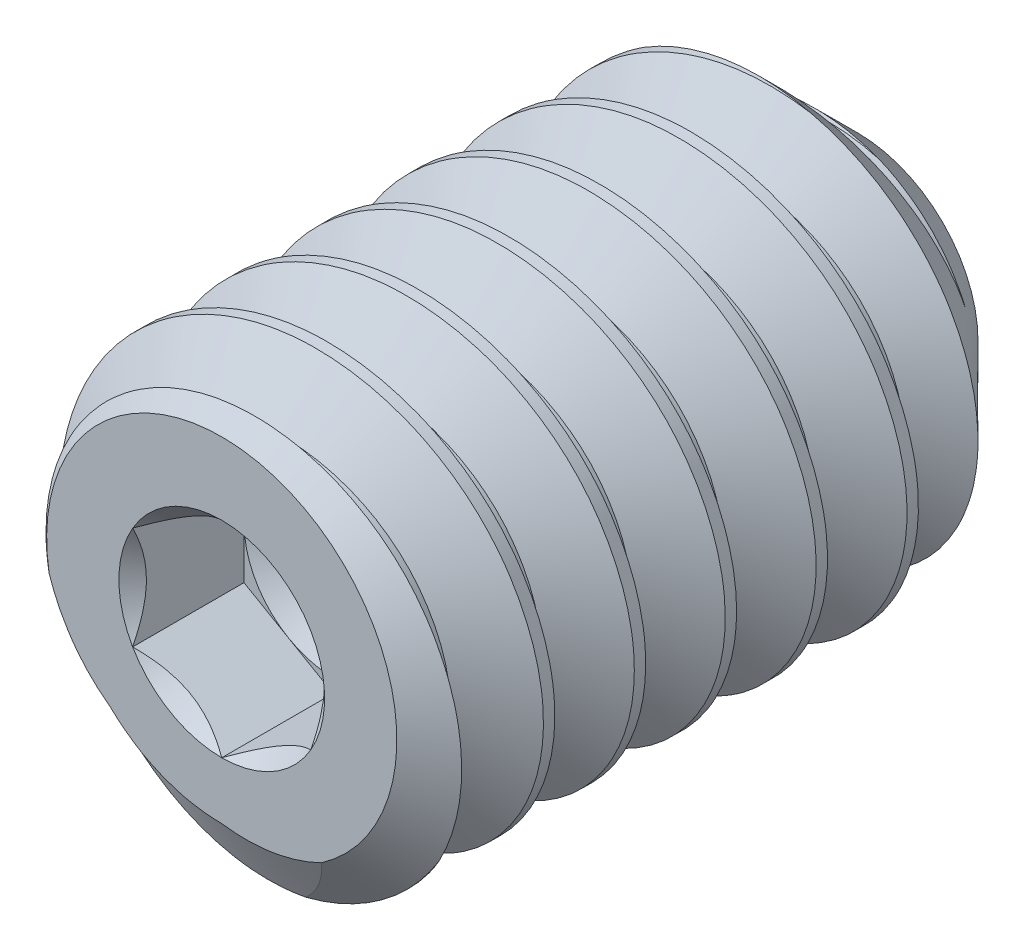
SolidWorks part; units mm, degrees
ref_plane "Front" through (0, 0, 0) normal (0, 0, 1) x (1, 0, 0)
ref_plane "Top" through (0, 0, 0) normal (0, 1, 0) x (1, 0, 0)
ref_plane "Right" through (0, 0, 0) normal (1, 0, 0) x (0, 0, -1)
sketch "Sketch22" plane through (0, 0, 0) normal (1, 0, 0) x (0, 0, -1)
  line L0 (-1.4077, 0) -> (-1.4077, 0.8738)
  line L1 (-1.4077, 0.8738) -> (-1.2547, 1.0922)
  line L2 (-1.2547, 1.0922) -> (1.2736, 1.0922)
  line L3 (1.2736, 1.0922) -> (1.7673, 0.5985)
  line L4 (1.7673, 0.5985) -> (1.4077, 0)
  line L5 (1.4077, 0) -> (-1.4077, 0)
  line L6 (1.4077, 0) -> (1.7673, 0) construction
  line L7 (1.7673, 0) -> (1.7673, 0.5985) construction
  line L8 (1.7673, -0.5985) -> (1.4077, 0) construction
  line L9 (-1.2547, -1.0922) -> (1.2736, -1.0922) construction
  dimension "Dia" = 2.1844
  dimension "Length" = 3.175
  dimension "D3" = 35
  dimension "D5" = 118
  dimension "D6" = 45
  dimension "D7" = 1.7475
revolve "Revolve1" add sketch "Sketch22" angle 360 about L6
ref_plane "Plane1" through (0, 0, -1.7673) normal (0, 0, 1) x (1, 0, 0)
sketch "Sketch27" plane through (0, 0, -1.7673) normal (0, 0, 1) x (1, 0, 0)
  circle A0 centre (0, 0) radius 1.0922 construction
  circle A1 centre (0, 0) radius 1.0922
curve "Helix/Spiral1" pitch 0.4536 height 3.6286 radius 1.0922 centre (0, 0, -1.7673) axis (0, 0, 1) start towards (0, 1, 0)
sketch "Sketch28" plane through (0, 0, 0) normal (1, 0, 0) x (0, 0, -1)
  line L0 (1.7673, 1.0922) -> (2.1642, 1.0922)
  line L1 (2.1642, 1.0922) -> (1.9941, 0.7976)
  line L2 (1.9941, 0.7976) -> (1.9374, 0.7976)
  line L3 (1.9374, 0.7976) -> (1.7673, 1.0922)
  line L4 (1.8523, 0.9449) -> (2.0791, 0.9449) construction
  line L6 (-1.2547, 1.0922) -> (1.2736, 1.0922) construction
  line L7 (1.7673, 1.2014) -> (1.7673, -1.2014) construction
  dimension "D3" = 60
  dimension "D2" = 0.2268
sweep "Cut-Sweep2" cut profiles "Sketch28" path "Helix/Spiral1" align with end faces yes
sketch "Sketch23" plane through (0, 0, 1.4077) normal (0, 0, 1) x (1, 0, 0)
  line L1 (0, 0.5133) -> (-0.4445, 0.2566)
  line L2 (-0.4445, 0.2566) -> (-0.4445, -0.2566)
  line L3 (-0.4445, -0.2566) -> (0, -0.5133)
  line L4 (0, -0.5133) -> (0.4445, -0.2566)
  line L5 (0.4445, -0.2566) -> (0.4445, 0.2566)
  line L6 (0.4445, 0.2566) -> (0, 0.5133)
  circle A0 centre (0, 0) radius 0.4445 construction
  dimension "Hex" = 0.889
extrude "Cut-Extrude10" cut sketch "Sketch23" against normal blind 0.5556
sketch "Sketch24" plane through (0, 0, 1.4077) normal (0, 0, 1) x (1, 0, 0)
  circle A0 centre (0, 0) radius 0.5133
extrude "Cut-Extrude11" cut sketch "Sketch24" against normal through all draft 45
sketch "Sketch26" plane through (0, 0, 0.8521) normal (0, 0, 1) x (1, 0, 0)
  circle A0 centre (0, 0) radius 0.4445 construction
  circle A1 centre (0, 0) radius 0.4445
extrude "Cut-Extrude12" cut sketch "Sketch26" against normal through all draft 60
sketch "Sketch30" plane through (0, 0, 0) normal (1, 0, 0) x (0, 0, -1)
  line L0 (-1.2547, 1.0922) -> (1.2736, 1.0922) construction
  line L1 (-1.4077, 0) -> (-1.4077, 0.8738) construction
  line L2 (1.7673, 0) -> (1.7673, 0.5985) construction
  line L3 (-1.2547, -1.0922) -> (1.2736, -1.0922) construction
  point P0 (-1.4077, 1.0922)
  point P1 (1.7673, 1.0922)
  point P2 (1.7673, -1.0922)
  point P11 (0.1798, -1.0922)
  dimension "D1" = 1.5875
sketch "Sketch31" plane through (0, 0, 0) normal (1, 0, 0) x (0, 0, -1)
  line L2 (1.4077, 0) -> (1.7673, -0.5985)
  line L3 (1.7673, 0.5985) -> (1.4077, 0)
equation "\"D7@Sketch22\"=\"Dia@Sketch22\"*.8"
equation "\"D1@Sketch28\" = \"D4@Helix/Spiral1\" * .125"
equation "\"D3@Helix/Spiral1\" = \"Length@Sketch22\" + \"D4@Helix/Spiral1\""
equation "\"D1@Sketch30\" = \"D4@Helix/Spiral1\" * 3.5"
equation "\"hex Depth@Cut-Extrude10\" = \"Hex@Sketch23\" * .625"
equation "\"D2@Sketch28\" = \"D4@Helix/Spiral1\" * .5"
